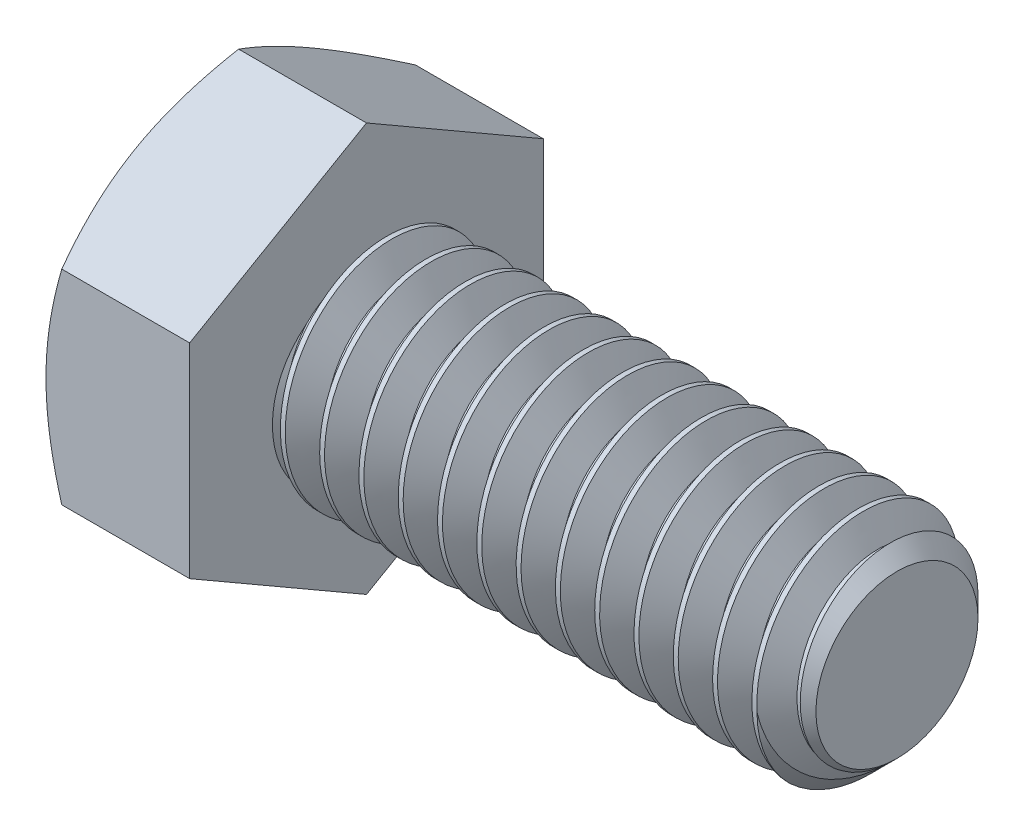
SolidWorks part; units mm, degrees
material "AISI 304"
ref_plane "Front Plane" through (0, 0, 0) normal (0, 0, 1) x (1, 0, 0)
ref_plane "Top Plane" through (0, 0, 0) normal (0, 1, 0) x (1, 0, 0)
ref_plane "Right Plane" through (0, 0, 0) normal (1, 0, 0) x (0, 0, -1)
sketch "Sketch1" plane through (0, 0, 0) normal (0, 0, 1) x (1, 0, 0)
  line L0 (-12.1047, 0) -> (12.1047, 0) construction
  line L1 (12.1047, 3.9688) -> (12.1047, -3.9688) construction
  line L2 (-6.9453, 6.35) -> (-6.9453, -6.35) construction
  line L3 (-12.1047, 6.35) -> (-12.1047, -6.35) construction
  point P9 (-6.9453, 0)
  point P10 (7.1658, -3.9688)
  dimension "D1" = 4.9389
  dimension "Screw Dia" = 7.9375
  dimension "Hex" = 12.7
  dimension "Head Ht" = 5.1594
  dimension "Screw Lenght" = 19.05
ref_plane "Plane2" through (12.1047, 0, 0) normal (1, 0, 0) x (0, 0, -1)
sketch "Sketch5" plane through (12.1047, 0, 0) normal (1, 0, 0) x (0, 0, -1)
  circle A0 centre (0, 0) radius 3.9688
extrude "Boss-Extrude3" add sketch "Sketch5" against normal up to vertex (19.05 mm away) up to point (-6.9453, 0, 0)
sketch "Sketch9" plane through (12.1047, 0, 0) normal (1, 0, 0) x (0, 0, -1)
  circle A1 centre (0, 0) radius 3.9688
  circle A2 centre (0, 0) radius 3.9688
  dimension "D1" = 0
curve "Helix/Spiral1" pitch 1.4111 height 20.4611 turns 14.5 parameters "Pitch"=1.4111
chamfer "Chamfer1" distance 1.0583 angle 45 1 edges at (12.1047, 0, -3.9688)
sketch "Sketch10" plane through (0, 0, 0) normal (0, 0, 1) x (1, 0, 0)
  line L0 (12.1047, 3.9688) -> (12.6339, 3.0522)
  line L1 (12.6339, 3.0522) -> (12.8102, 3.0522)
  line L2 (12.8102, 3.0522) -> (13.3394, 3.9688)
  line L3 (12.1047, 3.9688) -> (13.3394, 3.9688)
  line L4 (12.722, 3.9688) -> (12.722, 3.0522) construction
  line L5 (12.3693, 3.5105) -> (13.0748, 3.5105) construction
  dimension "D1" = 60
  dimension "D2" = 0.1764
  dimension "D3" = 0.7056
sweep "Cut-Sweep1" cut profiles "Sketch10" path "Helix/Spiral1"
sketch "Sketch6" plane through (-6.9453, 0, 0) normal (-1, 0, 0) x (0, 0, 1)
  line L0 (0, 6.35) -> (0, -6.35) construction
  line L1 (6.35, 3.6662) -> (0, 7.3323)
  line L2 (0, 7.3323) -> (-6.35, 3.6662)
  line L3 (-6.35, 3.6662) -> (-6.35, -3.6662)
  line L4 (-6.35, -3.6662) -> (0, -7.3323)
  line L5 (0, -7.3323) -> (6.35, -3.6662)
  line L6 (6.35, -3.6662) -> (6.35, 3.6662)
  circle A0 centre (0, 0) radius 6.35 construction
extrude "Boss-Extrude4" add sketch "Sketch6" along normal up to vertex (5.1594 mm away) up to point (-12.1047, -6.35, 0)
sketch "Sketch7" plane through (-12.1047, 0, 0) normal (-1, 0, 0) x (0, 0, 1)
  circle A0 centre (0, 0) radius 6.35 construction
  circle A1 centre (0, 0) radius 6.35
sketch "Sketch8" plane through (-12.1047, 0, 0) normal (-1, 0, 0) x (0, 0, 1)
  circle A0 centre (0, 0) radius 6.35 construction
  circle A1 centre (0, 0) radius 6.35
extrude "Cut-Extrude3" cut sketch "Sketch8" against normal through all draft 60 flip side to cut
equation "\"D2@Sketch10\" = \"Pitch@Helix/Spiral1\"*.125"
equation "\"D3@Sketch10\" = \"Pitch@Helix/Spiral1\"*.5"
equation "\"D3@Helix/Spiral1\" = \"Screw Lenght@Sketch1\"+\"Pitch@Helix/Spiral1\""
equation "\"D1@Chamfer1\" = \"Pitch@Helix/Spiral1\"*.75"
equation "\"D1@Sketch1\" = \"Pitch@Helix/Spiral1\"*3.5"
